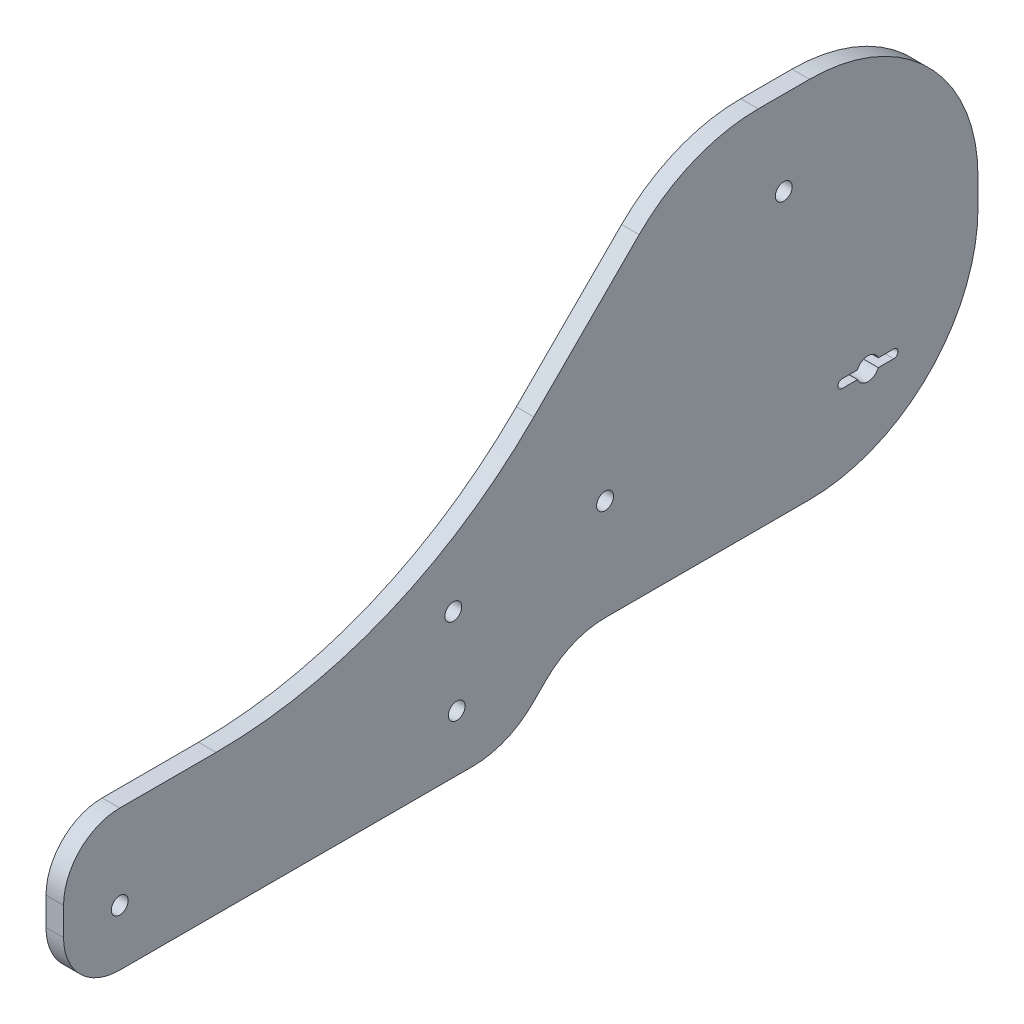
SolidWorks part; units mm, degrees
ref_plane "Front Plane" through (0, 0, 0) normal (0, 0, 1) x (1, 0, 0)
ref_plane "Top Plane" through (0, 0, 0) normal (0, 1, 0) x (1, 0, 0)
ref_plane "Right Plane" through (0, 0, 0) normal (1, 0, 0) x (0, 0, -1)
sketch "Sketch1" plane through (0, 0, 0) normal (1, 0, 0) x (0, 0, -1)
  line L0 (-62.0729, -10) -> (29.851, 81.9239) construction
  line L1 (29.851, 81.9239) -> (22.0729, 89.7021) construction
  line L2 (22.0729, 89.7021) -> (-69.851, -2.2218) construction
  line L3 (-69.851, -2.2218) -> (-62.0729, -10) construction
  line L4 (-4.6, 0) -> (4.6, 0) construction
  line L5 (-6, 5) -> (-6, -5) construction
  line L6 (-4.6, 0.75) -> (-1.854, 0.75)
  line L7 (-4.6, -0.75) -> (-1.854, -0.75)
  line L8 (-6, -5) -> (6, -5) construction
  line L9 (1.854, 0.75) -> (4.6, 0.75)
  line L10 (1.854, -0.75) -> (4.6, -0.75)
  line L11 (6, -5) -> (6, 5) construction
  line L12 (6, 5) -> (-6, 5) construction
  line L13 (-6, 5) -> (6, -5) construction
  line L14 (-69.851, -2.2218) -> (29.851, 81.9239) construction
  line L15 (-20, 39.851) -> (-20, 79.8794) construction
  line L16 (-9.747, 57.8823) -> (-1.9688, 50.1041) construction
  line L17 (-46.7993, 3.0108) -> (-14.9795, 34.8306) construction
  line L18 (-73.2042, -16.1314) -> (-133.2042, -16.1314) construction
  line L19 (-73.8108, -0.5248) -> (-63.2042, -11.1314) construction
  line L20 (-62.0729, -10) -> (-63.2042, -11.1314) construction
  line L21 (-143.2042, -1.1314) -> (-143.2042, -26.1314)
  line L22 (-143.2042, -26.1314) -> (-64.0621, -26.1314)
  line L23 (-64.0621, -26.1314) -> (-52.9307, -15)
  line L24 (-52.9307, -15) -> (19.6, -15)
  line L25 (19.6, -15) -> (19.6, 49.8306)
  line L26 (19.6, 49.8306) -> (-31.9408, 49.8306)
  line L27 (-31.9408, 49.8306) -> (-82.9027, -1.1314)
  line L28 (-82.9027, -1.1314) -> (-143.2042, -1.1314)
  line L29 (0, -31) -> (-153.4899, -31) construction
  arc A0 (-1.854, -0.75) -> (1.854, -0.75) centre (0, 0) ccw
  arc A1 (-4.6, 0.75) -> (-4.6, -0.75) centre (-4.6, 0) ccw
  arc A2 (1.854, 0.75) -> (-1.854, 0.75) centre (0, 0) ccw
  circle A3 centre (0, 0) radius 31 construction
  arc A4 (4.6, -0.75) -> (4.6, 0.75) centre (4.6, 0) ccw
  circle A5 centre (-46.7993, 3.0108) radius 1.5
  circle A6 centre (-14.9795, 34.8306) radius 1.5
  circle A7 centre (-73.8108, -0.5248) radius 1.5
  circle A8 centre (-73.2042, -16.1314) radius 1.5
  circle A9 centre (-133.2042, -16.1314) radius 1.5
  point P11 (-4.6, 0)
  point P16 (4.6, 0)
  point P43 (-60.3276, -26.1314)
  dimension "D4" = 4
  dimension "D5" = 0.75
  dimension "D9" = 62
  dimension "D14" = 3
  dimension "D15" = 1.6
  dimension "D1" = 11
  dimension "D2" = 130
  dimension "D3" = 9.2
  dimension "D6" = 10
  dimension "D7" = 12
  dimension "D8" = 45
  dimension "D10" = 20
  dimension "D11" = 10
  dimension "D12" = 45
  dimension "D13" = 1.6
  dimension "D16" = 20
  dimension "D17" = 65
  dimension "D18" = 15
  dimension "D19" = 5
  dimension "D20" = 10
  dimension "D21" = 60
  dimension "D22" = 10
  dimension "D23" = 15
  dimension "D24" = 10
  dimension "D25" = 15
  dimension "D26" = 10
  dimension "D27" = 15
  dimension "D28" = 15
  dimension "D29" = 10
  dimension "D30" = 45
extrude "Boss-Extrude1" add sketch "Sketch1" along normal blind 3.125
fillet "Fillet1" radius 10 2 edges at (1.5625, -1.1314, 143.2042) (1.5625, -26.1314, 143.2042)
fillet "Fillet2" radius 15 2 edges at (1.5625, -26.1314, 64.0621) (1.5625, -15, 52.9307)
fillet "Fillet3" radius 30 1 edges at (1.5625, -15, -19.6)
fillet "Fillet4" radius 30 1 edges at (1.5625, 49.8306, 31.9408)
fillet "Fillet5" radius 80 1 edges at (1.5625, -1.1314, 82.9027)
fillet "Fillet6" radius 30 1 edges at (1.5625, 49.8306, -19.6)
